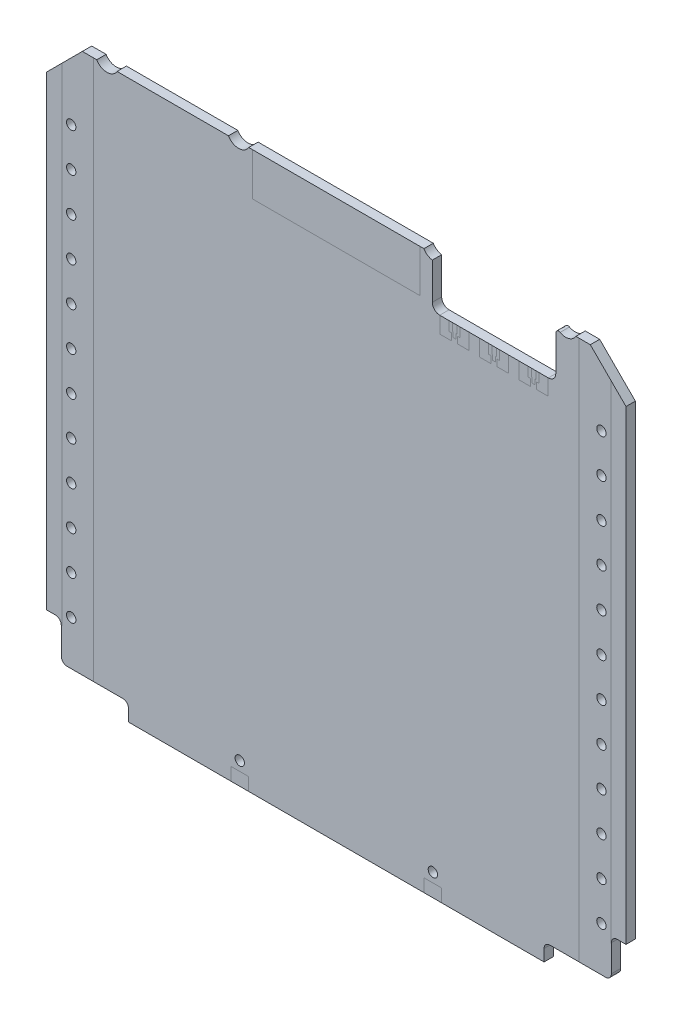
SolidWorks part; units mm, degrees
material "FR4_stuffedProtoboard"
ref_plane "Front Plane" through (0, 0, 0) normal (0, 0, 1) x (1, 0, 0)
ref_plane "Top Plane" through (0, 0, 0) normal (0, 1, 0) x (1, 0, 0)
ref_plane "Right Plane" through (0, 0, 0) normal (1, 0, 0) x (0, 0, -1)
ref_plane "Plane4" through (0, 0, -0.0125) normal (0, 0, -1) x (-1, 0, 0)
sketch "Sketch1" plane through (0, 0, -0.0125) normal (0, 0, -1) x (-1, 0, 0)
  line L4 (49.5, -50) -> (49.5, 45.3)
  line L6 (49.5, 45.3) -> (-49.5, 45.3)
  line L12 (-49.5, 45.3) -> (-49.5, -50)
  line L17 (-49.5, -50) -> (49.5, -50)
  line L18 (0, -50) -> (0, 45.3) construction
  dimension "D7" = 95.3
  dimension "D1" = 99
  dimension "D34" = 50
extrude "basicSize" add sketch "Sketch1" against normal blind 1.6
chamfer "Chamfer1" distance 6.1 angle 45 2 edges at (49.5, 45.3, 0.7875) (-49.5, 45.3, 0.7875)
sketch "Sketch4" plane through (0, 0, 1.5875) normal (0, 0, 1) x (1, 0, 0)
  line L1 (37.4679, 45.3) -> (40.9321, 45.3)
  line L7 (-43.4, 45.3) -> (43.4, 45.3) construction
  line L8 (49.5, 39.2) -> (49.5, -50) construction
  arc A0 (40.9321, 45.3) -> (37.4679, 45.3) centre (39.2, 46.3) cw
  point P5 (39.2, 44.3)
  dimension "D1" = 2
  dimension "D3" = 10.3
  dimension "D2" = 1
extrude "backplaneSideScrewCutout" cut sketch "Sketch4" against normal through all both and the other way through all
pattern_linear "LPattern3" count 2 spacing 22.5 along (-1, 0, 0) of "backplaneSideScrewCutout"
mirror "Mirror3" about plane through (0, 0, 0) normal (1, 0, 0) of "LPattern3"
sketch "Sketch6" plane through (0, 0, 1.5875) normal (0, 0, 1) x (1, 0, 0)
  line L0 (-49.5, -50) -> (-49.5, 39.2) construction
  line L1 (-49.5, -40.4) -> (-47, -40.4)
  line L2 (-49.5, -40.4) -> (-49.5, -50)
  line L4 (-47, -40.4) -> (-47, -47)
  line L5 (49.5, -50) -> (-49.5, -50) construction
  line L6 (-35.5, -50) -> (-49.5, -50)
  line L7 (-35.5, -50) -> (-35.5, -47)
  line L8 (-35.5, -47) -> (-47, -47)
  dimension "D1" = 2.5
  dimension "D2" = 3
  dimension "D3" = 9.6
  dimension "D4" = 14
extrude "Cut-Extrude4" cut sketch "Sketch6" against normal through all
fillet "Fillet1" radius 1 3 edges at (-35.5, -47, 0.7875) (-47, -47, 0.7875) (-47, -40.4, 0.7875)
mirror "Mirror1" about plane through (0, 0, 0) normal (1, 0, 0) of "Cut-Extrude4", "Fillet1"
sketch "Sketch7" plane through (0, 0, 1.5875) normal (0, 0, 1) x (1, 0, 0)
  line L0 (-14.2875, 45.5) -> (-14.2875, 39.912) construction
  line L1 (-14.2875, 45.3) -> (-14.2875, 38.007)
  line L2 (-12.2428, 38.007) -> (-11.8872, 38.007) construction
  line L3 (-14.2875, 38.007) -> (14.2875, 38.007)
  line L4 (14.2875, 45.5) -> (14.2875, 39.912) construction
  line L5 (14.2875, 45.3) -> (14.2875, 38.007)
  line L7 (-14.9679, 45.3) -> (14.9679, 45.3) construction
  line L8 (-14.2875, 45.3) -> (14.2875, 45.3)
extrude "TigerEyeFootprint" cut sketch "Sketch7" against normal blind 0.0001
sketch "thermalContacts_upper" plane through (0, 0, 1.5875) normal (0, 0, 1) x (1, 0, 0)
  line L0 (-49.5, -40.4) -> (-49.5, 39.2) construction
  line L1 (35.5, -50) -> (-35.5, -50) construction
  line L3 (-46.9, 45.3) -> (-46.9, -41.5)
  line L4 (-37.4679, 45.3) -> (-18.4321, 45.3) construction
  line L23 (-46.9, 45.3) -> (-56.3922, 45.3)
  line L24 (-56.3922, 45.3) -> (-56.3922, -41.5)
  line L25 (-56.3922, -41.5) -> (-46.9, -41.5)
  dimension "D1" = 2.6
  dimension "D2" = 8.5
extrude "keepOut_bottom" cut sketch "thermalContacts_upper" against normal blind 0.0001
sketch "Sketch3" plane through (0, 0, 1.5875) normal (0, 0, 1) x (1, 0, 0)
  line L1 (-47, -46) -> (-47, -41.5) construction
  line L2 (-36.5, -47) -> (-46, -47) construction
  line L3 (-14.9679, 45.3) -> (14.9679, 45.3) construction
  line L5 (-49.5, -40.4) -> (-49.5, 39.2) construction
  line L6 (-46.9, -41.5) -> (-46.9, 41.8) construction
  line L7 (-46.9, -41.5) -> (-47, -41.5)
  line L8 (-47, -46) -> (-47, -41.5) construction
  line L9 (-47, -41.5) -> (-46.9, -41.5) construction
  line L10 (0, -50) -> (0, 45.3) construction
  line L11 (35.5, -50) -> (-35.5, -50) construction
  line L12 (-43.4, 45.3) -> (-40.9321, 45.3) construction
  line L13 (-41.5, 45.3) -> (-46.9, 45.3)
  line L14 (-46, -47) -> (-41.5, -47)
  line L15 (-47, -41.5) -> (-47, -46)
  line L16 (-46.9, 45.3) -> (-46.9, -41.5)
  line L17 (-41.5, -47) -> (-41.5, 45.3)
  arc A3 (-47, -46) -> (-46, -47) centre (-46, -46) ccw construction
  arc A4 (-46, -47) -> (-47, -46) centre (-46, -46) cw
  dimension "D1" = 8
extrude "caution_top" cut sketch "Sketch3" against normal blind 0.0001
sketch "hold-downLocations" plane through (0, 0, 1.5875) normal (0, 0, 1) x (1, 0, 0)
  line L1 (-18, -47.8) -> (-15, -47.8) construction
  line L3 (15, -47.8) -> (18, -47.8)
  line L4 (18, -47.8) -> (18, -50)
  line L5 (35.5, -50) -> (-35.5, -50) construction
  line L6 (18, -50) -> (15, -50)
  line L7 (15, -50) -> (15, -47.8)
  line L8 (-15, -47.8) -> (-15, -50) construction
  line L9 (-15, -50) -> (-18, -50) construction
  line L10 (-18, -50) -> (-18, -47.8) construction
  line L11 (0, -50) -> (0, -47.8) construction
  line L12 (-15, -47.8) -> (15, -47.8) construction
  dimension "D1" = 3
  dimension "D2" = 2.2
  dimension "D3" = 3
  dimension "D5" = 30
extrude "hold-downFootprints" cut sketch "hold-downLocations" against normal blind 0.0001
ref_plane "midplane_Z" through (0, 0, 0.7875) normal (0, 0, 1) x (1, 0, 0)
mirror "clearances_top-bottom" about plane through (0, 0, 0.7875) normal (0, 0, 1) of "hold-downFootprints", "caution_top", "keepOut_bottom"
mirror "clearances_side-side" about plane through (0, 0, 0) normal (1, 0, 0) of "clearances_top-bottom"
sketch "Sketch10" plane through (0, 0, -0.0125) normal (0, 0, -1) x (-1, 0, 0)
  line L0 (-15, -47.8) -> (-15, -50) construction
  line L1 (-18, -47.8) -> (-15, -47.8)
  line L2 (-18, -47.8) -> (-18, -44.5)
  line L3 (-18, -44.5) -> (-15, -44.5)
  line L4 (-15, -47.8) -> (-15, -44.5)
  line L5 (-15, -50) -> (15, -50) construction
  line L6 (0, -50) -> (0, -41.5199) construction
  line L7 (15, -47.8) -> (15, -44.5)
  line L8 (18, -44.5) -> (15, -44.5)
  line L9 (18, -47.8) -> (18, -44.5)
  line L10 (18, -47.8) -> (15, -47.8)
  dimension "D1" = 5.5
extrude "bottomsideShelfKeepouts" cut sketch "Sketch10" against normal up to surface (0.0001 mm away) up to face at (16.5, -48.9, -0.0124)
sketch "recommendedBuildArea" [suppressed] plane through (0, 0, 1.5875) normal (0, 0, 1) x (1, 0, 0)
  line L0 (51.1146, 38.007) -> (51.1146, 56.8216) construction
  line L1 (-35.5, -45.5) -> (-46.8, -45.5) construction
  line L2 (-35.5, -47) -> (-35.5, -45.5) construction
  line L3 (35.5, -47) -> (35.5, -45.5) construction
  line L4 (14.2875, 45.3) -> (-14.2875, 45.3)
  line L5 (-14.2875, 45.3) -> (-14.2875, 38.007)
  line L6 (-14.2875, 38.007) -> (14.2875, 38.007)
  line L7 (-46.8, 41.9) -> (-49.5, 39.2)
  line L8 (-49.5, 39.2) -> (-49.5, -40.4)
  line L9 (-49.5, -40.4) -> (-48, -40.4)
  line L10 (-46.8, -41.5) -> (-46.8, 41.9)
  line L11 (-47, -41.4) -> (-47, -41.5)
  line L12 (-47, -41.4) -> (-47, -41.5)
  line L13 (-47, -41.5) -> (-46.8, -41.5)
  line L14 (35.5, -45.5) -> (46.8, -45.5) construction
  line L15 (54.1146, 35.007) -> (54.1146, 77.997)
  line L16 (54.1146, 77.997) -> (43.8, 42.325)
  line L17 (-46.8, -45.5) -> (-46.8, 41.9) construction
  line L20 (43.8, 42.325) -> (43.8, -42.5)
  line L21 (14.2875, 38.007) -> (14.2875, 45.3)
  line L22 (32.5, -42.5) -> (43.8, -42.5)
  line L23 (-14.2875, 45.3) -> (-14.2875, 38.007)
  line L24 (-14.2875, 38.007) -> (51.1146, 38.007)
  line L25 (32.5, -47) -> (32.5, -42.5)
  line L26 (32.5, -47) -> (32.5, -47)
  line L27 (21, -47) -> (32.5, -47)
  line L28 (21, -45) -> (21, -47)
  line L29 (46.8, -41.5) -> (47, -41.5)
  line L30 (46.8, -41.5) -> (47, -41.5)
  line L31 (46.8, 41.9) -> (46.8, -41.5)
  line L32 (48, -40.4) -> (49.5, -40.4)
  line L33 (49.5, -40.4) -> (49.5, 39.2)
  line L34 (49.5, 39.2) -> (46.8, 41.9)
  line L35 (47, -41.5) -> (47, -41.4)
  line L36 (12, -45) -> (21, -45)
  line L37 (47, -41.5) -> (47, -41.4)
  line L38 (46.8, 41.9) -> (46.8, -45.5) construction
  line L39 (12, -47) -> (12, -45)
  line L40 (-12, -47) -> (12, -47)
  line L41 (-12, -45) -> (-12, -47)
  line L42 (-21, -45) -> (-12, -45)
  line L43 (-21, -47) -> (-21, -45)
  line L44 (-32.5, -47) -> (-21, -47)
  line L45 (-32.5, -47) -> (-32.5, -47)
  line L46 (-32.5, -47) -> (-32.5, -42.5)
  line L47 (-32.5, -42.5) -> (-43.8, -42.5)
  line L48 (-43.8, -42.5) -> (-43.8, 34.7661)
  line L49 (-43.8, 34.7661) -> (-43.8, 34.7661)
  line L50 (-43.8, 34.7661) -> (-39.8793, 42.3)
  line L51 (-17.2875, 42.3) -> (-39.8793, 42.3)
  line L52 (-17.2875, 42.3) -> (-17.2875, 35.007)
  line L53 (-17.2875, 35.007) -> (54.1146, 35.007)
  line L59 (-47, -41.5) -> (-46.8, -41.5)
  line L72 (-15, -48) -> (-15, -50)
  line L73 (-15, -50) -> (15, -50)
  line L74 (15, -50) -> (15, -48)
  line L75 (15, -48) -> (18, -48)
  line L76 (18, -48) -> (18, -50)
  line L77 (18, -50) -> (35.5, -50)
  line L78 (35.5, -50) -> (35.5, -48)
  line L79 (36.5, -47) -> (41.5, -47)
  line L80 (41.5, -47) -> (41.5, 45.3)
  line L81 (41.5, 45.3) -> (40.9321, 45.3)
  line L82 (37.4679, 45.3) -> (34.25, 45.3)
  line L83 (34.25, 45.3) -> (34.25, 38.35)
  line L84 (34.25, 38.35) -> (30.75, 38.35)
  line L85 (30.75, 38.35) -> (30.75, 45.3)
  line L86 (30.75, 45.3) -> (29.25, 45.3)
  line L87 (29.25, 45.3) -> (29.25, 38.35)
  line L88 (29.25, 38.35) -> (25.75, 38.35)
  line L89 (25.75, 38.35) -> (25.75, 45.3)
  line L90 (25.75, 45.3) -> (24.25, 45.3)
  line L91 (24.25, 45.3) -> (24.25, 38.35)
  line L92 (24.25, 38.35) -> (20.75, 38.35)
  line L93 (20.75, 38.35) -> (20.75, 45.3)
  line L94 (20.75, 45.3) -> (18.4321, 45.3)
  line L95 (14.9679, 45.3) -> (14.2875, 45.3)
  line L96 (14.2875, 45.3) -> (14.2875, 38.007)
  line L97 (14.2875, 38.007) -> (-14.2875, 38.007)
  line L98 (-14.2875, 38.007) -> (-14.2875, 45.3)
  line L99 (-14.2875, 45.3) -> (-14.9679, 45.3)
  line L100 (-18.4321, 45.3) -> (-37.4679, 45.3)
  line L101 (-40.9321, 45.3) -> (-41.5, 45.3)
  line L102 (41.5, -47) -> (41.5, 45.3)
  line L103 (-41.5, -47) -> (-36.5, -47)
  line L104 (-35.5, -48) -> (-35.5, -50)
  line L105 (-35.5, -50) -> (-18, -50)
  line L106 (-18, -50) -> (-18, -48)
  line L107 (-18, -48) -> (-15, -48)
  line L108 (-15, -48) -> (-15, -50) construction
  line L109 (-15, -50) -> (15, -50) construction
  line L110 (15, -50) -> (15, -48) construction
  line L111 (15, -48) -> (18, -48) construction
  line L112 (18, -48) -> (18, -50) construction
  line L113 (18, -50) -> (35.5, -50) construction
  line L114 (35.5, -50) -> (35.5, -47) construction
  line L115 (35.5, -47) -> (41.5, -47) construction
  line L133 (51.1146, 38.007) -> (-14.2875, 38.007)
  line L134 (-14.2875, 38.007) -> (-14.2875, 45.3)
  line L136 (-14.2875, 45.3) -> (-41.7, 45.3) construction
  line L139 (-41.5, -47) -> (-35.5, -47) construction
  line L140 (-35.5, -47) -> (-35.5, -50) construction
  line L141 (-35.5, -50) -> (-18, -50) construction
  line L142 (-18, -50) -> (-18, -48) construction
  line L143 (-18, -48) -> (-15, -48) construction
  line L144 (-46.8, 35.5) -> (-41.7, 45.3) construction
  line L160 (-41.5, 45.3) -> (-41.5, -47)
  line L161 (-41.5, 45.3) -> (-41.5, -47)
  line L162 (-46.8, 41.9) -> (-46.8, 35.5) construction
  line L163 (51.1146, 56.8216) -> (46.8, 41.9) construction
  arc A1 (-47, -41.4) -> (-48, -40.4) centre (-48, -41.4) ccw
  arc A3 (48, -40.4) -> (47, -41.4) centre (48, -41.4) ccw
  arc A10 (36.5, -47) -> (35.5, -48) centre (36.5, -48) ccw
  arc A11 (37.4679, 45.3) -> (40.9321, 45.3) centre (39.2, 46.3) ccw
  arc A12 (14.9679, 45.3) -> (18.4321, 45.3) centre (16.7, 46.3) ccw
  arc A13 (-18.4321, 45.3) -> (-14.9679, 45.3) centre (-16.7, 46.3) ccw
  arc A14 (-40.9321, 45.3) -> (-37.4679, 45.3) centre (-39.2, 46.3) ccw
  arc A15 (-35.5, -48) -> (-36.5, -47) centre (-36.5, -48) ccw
  dimension "D5" = 1.5
  dimension "D1" = 0
  dimension "D2" = 0
  dimension "D3" = 0
  dimension "D4" = 0
  dimension "D6" = 3
ref_point "rail midpoint"
sketch "locatorSketch" plane through (0, 0, 1.5875) normal (0, 0, 1) x (1, 0, 0)
  line L0 (-12.2428, 39.531) -> (12.2428, 38.007) construction
  line L1 (12.2428, 39.531) -> (-12.2428, 38.007) construction
  line L2 (-21.9628, 39.277) -> (-33.0372, 38.261) construction
  line L3 (-33.0372, 39.277) -> (-21.9628, 38.261) construction
  line L4 (-12.2428, 38.261) -> (-12.2428, 38.007)
  line L5 (-11.8872, 38.261) -> (-12.2428, 38.261)
  line L6 (-11.8872, 38.007) -> (-11.8872, 38.261)
  line L7 (-12.2428, 38.007) -> (-11.8872, 38.007)
  line L8 (-12.2428, 38.261) -> (-12.2428, 38.007)
  line L9 (-11.8872, 38.261) -> (-12.2428, 38.261)
  line L10 (-11.8872, 38.007) -> (-11.8872, 38.261)
  line L11 (-12.2428, 38.007) -> (-11.8872, 38.007)
  line L12 (-12.2428, 39.531) -> (-12.2428, 39.277)
  line L13 (-11.8872, 39.531) -> (-12.2428, 39.531)
  line L14 (-11.8872, 39.277) -> (-11.8872, 39.531)
  line L15 (-12.2428, 39.277) -> (-11.8872, 39.277)
  line L16 (-12.2428, 39.531) -> (-12.2428, 39.277)
  line L17 (-11.8872, 39.531) -> (-12.2428, 39.531)
  line L18 (-11.8872, 39.277) -> (-11.8872, 39.531)
  line L19 (-12.2428, 39.277) -> (-11.8872, 39.277)
  line L20 (11.8872, 39.531) -> (11.8872, 39.277)
  line L21 (12.2428, 39.531) -> (11.8872, 39.531)
  line L22 (12.2428, 39.277) -> (12.2428, 39.531)
  line L23 (11.8872, 39.277) -> (12.2428, 39.277)
  line L24 (11.8872, 39.531) -> (11.8872, 39.277)
  line L25 (12.2428, 39.531) -> (11.8872, 39.531)
  line L26 (12.2428, 39.277) -> (12.2428, 39.531)
  line L27 (11.8872, 39.277) -> (12.2428, 39.277)
  line L28 (11.8872, 38.261) -> (11.8872, 38.007)
  line L29 (12.2428, 38.261) -> (11.8872, 38.261)
  line L30 (12.2428, 38.007) -> (12.2428, 38.261)
  line L31 (11.8872, 38.007) -> (12.2428, 38.007)
  line L32 (11.8872, 38.261) -> (11.8872, 38.007)
  line L33 (12.2428, 38.261) -> (11.8872, 38.261)
  line L34 (12.2428, 38.007) -> (12.2428, 38.261)
  line L35 (11.8872, 38.007) -> (12.2428, 38.007)
  line L38 (-21.9628, 39.531) -> (-21.9628, 39.277)
  line L39 (-21.6072, 39.531) -> (-21.9628, 39.531)
  line L40 (-21.6072, 39.277) -> (-21.6072, 39.531)
  line L41 (-21.9628, 39.277) -> (-21.6072, 39.277)
  line L42 (-21.9628, 39.531) -> (-21.9628, 39.277)
  line L43 (-21.6072, 39.531) -> (-21.9628, 39.531)
  line L44 (-21.6072, 39.277) -> (-21.6072, 39.531)
  line L45 (-21.9628, 39.277) -> (-21.6072, 39.277)
  line L46 (-33.3928, 38.261) -> (-33.3928, 38.007)
  line L47 (-33.0372, 38.261) -> (-33.3928, 38.261)
  line L48 (-33.0372, 38.007) -> (-33.0372, 38.261)
  line L49 (-33.3928, 38.007) -> (-33.0372, 38.007)
  line L50 (-33.3928, 38.261) -> (-33.3928, 38.007)
  line L51 (-33.0372, 38.261) -> (-33.3928, 38.261)
  line L52 (-33.0372, 38.007) -> (-33.0372, 38.261)
  line L53 (-33.3928, 38.007) -> (-33.0372, 38.007)
  line L55 (-21.9628, 38.261) -> (-21.9628, 38.007)
  line L56 (-21.6072, 38.261) -> (-21.9628, 38.261)
  line L57 (-21.6072, 38.007) -> (-21.6072, 38.261)
  line L58 (-21.9628, 38.007) -> (-21.6072, 38.007)
  line L59 (-21.9628, 38.261) -> (-21.9628, 38.007)
  line L60 (-21.6072, 38.261) -> (-21.9628, 38.261)
  line L61 (-21.6072, 38.007) -> (-21.6072, 38.261)
  line L62 (-21.9628, 38.007) -> (-21.6072, 38.007)
  line L63 (-33.3928, 39.531) -> (-33.3928, 39.277)
  line L64 (-33.0372, 39.531) -> (-33.3928, 39.531)
  line L65 (-33.0372, 39.277) -> (-33.0372, 39.531)
  line L66 (-33.3928, 39.277) -> (-33.0372, 39.277)
  line L67 (-33.3928, 39.531) -> (-33.3928, 39.277)
  line L68 (-33.0372, 39.531) -> (-33.3928, 39.531)
  line L69 (-33.0372, 39.277) -> (-33.0372, 39.531)
  line L70 (-33.3928, 39.277) -> (-33.0372, 39.277)
  dimension "D1" = 0
  dimension "D2" = 0
  dimension "D3" = 0
  dimension "D4" = 0
  dimension "D5" = 0
  dimension "D6" = 0
  dimension "D7" = 0
  dimension "D8" = 0
sketch "Sketch8" plane through (0, 0, 1.5875) normal (0, 0, 1) x (1, 0, 0)
  line L0 (-49.5, -40.4) -> (-48, -40.4) construction
  line L2 (-49.5, -40.4) -> (-49.5, 39.2) construction
  line L3 (-41.5, 45.3) -> (-43.4, 45.3) construction
  line L4 (-18, -47.8) -> (-15, -47.8) construction
  line L5 (-45.3, 33.5) -> (-46.9, 33.5) construction
  line L6 (-46.9, 41.8) -> (-46.9, -41.5) construction
  line L7 (-16.5, -46.2) -> (-16.5, -47.8) construction
  line L8 (-18, -47.8) -> (-15, -47.8) construction
  circle A0 centre (-45.3, 33.5) radius 0.8
  circle A1 centre (-45.3, 26.8727) radius 0.8
  circle A2 centre (-45.3, 20.2455) radius 0.8
  circle A3 centre (-45.3, 13.6182) radius 0.8
  circle A4 centre (-45.3, 6.9909) radius 0.8
  circle A5 centre (-45.3, 0.3636) radius 0.8
  circle A6 centre (-45.3, -6.2636) radius 0.8
  circle A7 centre (-45.3, -12.8909) radius 0.8
  circle A8 centre (-45.3, -19.5182) radius 0.8
  circle A9 centre (-45.3, -26.1455) radius 0.8
  circle A10 centre (-45.3, -32.7727) radius 0.8
  circle A11 centre (-45.3, -39.4) radius 0.8
  circle A12 centre (-16.5, -46.2) radius 0.8
  point P35 (-16.5, -47.8)
  dimension "D1" = 1.6
  dimension "D3" = 1
  dimension "D5" = 4.2
  dimension "D6" = 11.8
  dimension "D2" = 12
extrude "springPinHoleSeed" cut sketch "Sketch8" against normal blind 10
mirror "Mirror4" about plane through (0, 0, 0) normal (1, 0, 0) of "springPinHoleSeed"
sketch "Sketch9" plane through (0, 0, 1.5875) normal (0, 0, 1) x (1, 0, 0)
  circle A0 centre (-45.3, 33.5) radius 1.35
  dimension "D1" = 2.7
sketch "bottomsideKeepout_trace" plane through (0, 0, -0.0125) normal (0, 0, -1) x (-1, 0, 0)
  line L0 (18, -50) -> (18, -44.5) construction
  line L1 (18, -44.5) -> (15, -44.5) construction
  line L2 (15, -44.5) -> (15, -50) construction
  line L3 (-15, -44.5) -> (-15, -50) construction
  line L4 (-15, -44.5) -> (-18, -44.5) construction
  line L5 (-18, -50) -> (-18, -44.5) construction
  line L6 (18, -50) -> (18, -44.5)
  line L7 (18, -44.5) -> (15, -44.5)
  line L8 (15, -44.5) -> (15, -50)
  line L9 (-15, -44.5) -> (-15, -50)
  line L10 (-15, -44.5) -> (-18, -44.5)
  line L11 (-18, -50) -> (-18, -44.5)
  line L12 (15, -50) -> (18, -50) construction
  line L13 (-15, -50) -> (-18, -50) construction
  line L14 (15, -50) -> (18, -50)
  line L15 (-15, -50) -> (-18, -50)
sketch "Sketch11" plane through (0, 0, 1.5875) normal (0, 0, 1) x (1, 0, 0)
  line L0 (18.4321, 45.3) -> (37.4679, 45.3) construction
  line L1 (16.4, 45.3) -> (37.5, 45.3)
  line L2 (16.4, 45.3) -> (16.4, 36.8)
  line L3 (16.4, 36.8) -> (24.95, 36.8)
  line L4 (37.5, 45.3) -> (37.5, 36.8)
  line L5 (16.4, 45.3) -> (37.5, 36.8) construction
  line L6 (16.4, 36.8) -> (37.5, 45.3) construction
  line L7 (49.5, 39.2) -> (49.5, -40.4) construction
  line L8 (26.95, 36.8) -> (26.95, 45.3) construction
  line L9 (24.95, 36.8) -> (28.95, 36.8)
  line L10 (28.95, 36.8) -> (37.5, 36.8)
  point P4 (26.95, 41.05)
  point P9 (0, 0)
  point P10 (0, 0)
  point P12 (28.8548, 36.8)
  point P21 (0, 0)
  dimension "D1" = 21.1
  dimension "D2" = 12
  dimension "D3" = 8.5
  dimension "D4" = 4
extrude "Cut-Extrude5" cut sketch "Sketch11" against normal blind 10
fillet "Fillet3" radius 1.27 2 edges at (37.5, 36.8, 0.7875) (16.4, 36.8, 0.7875)
sketch "Sketch12" plane through (0, 0, 1.5875) normal (0, 0, 1) x (1, 0, 0)
  line L0 (17.67, 36.8) -> (36.23, 36.8) construction
  line L1 (19.25, 36.8) -> (17.75, 36.8)
  line L2 (19.25, 36.8) -> (19.25, 35.2)
  line L3 (19.25, 35.2) -> (17.75, 35.2)
  line L4 (17.75, 36.8) -> (17.75, 35.2)
  line L5 (19.25, 36.8) -> (17.75, 35.2) construction
  line L6 (19.25, 35.2) -> (17.75, 36.8) construction
  line L7 (20.2, 36.8) -> (20.2, 34.2278) construction
  line L8 (20.585, 36.8) -> (19.815, 36.8)
  line L9 (20.585, 36.8) -> (20.585, 35.5)
  line L10 (20.585, 35.5) -> (19.815, 35.5)
  line L11 (19.815, 36.8) -> (19.815, 35.5)
  line L12 (20.585, 36.8) -> (19.815, 35.5) construction
  line L13 (20.585, 35.5) -> (19.815, 36.8) construction
  line L14 (21.15, 36.8) -> (22.65, 36.8)
  line L15 (21.15, 36.8) -> (21.15, 35.2)
  line L16 (21.15, 35.2) -> (22.65, 35.2)
  line L17 (22.65, 36.8) -> (22.65, 35.2)
  line L18 (21.15, 36.8) -> (22.65, 35.2) construction
  line L19 (21.15, 35.2) -> (22.65, 36.8) construction
  line L21 (22.65, 35.2) -> (20.725, 35.2)
  line L22 (22.65, 35.2) -> (22.65, 34.069)
  line L23 (22.65, 34.069) -> (20.725, 34.069)
  line L24 (20.725, 35.2) -> (20.725, 34.069)
  line L25 (22.65, 35.2) -> (20.725, 34.069) construction
  line L26 (22.65, 34.069) -> (20.725, 35.2) construction
  line L27 (20.43, 35.5) -> (19.97, 35.5)
  line L28 (20.43, 35.5) -> (20.43, 34.6345)
  line L29 (20.43, 34.6345) -> (19.97, 34.6345)
  line L30 (19.97, 35.5) -> (19.97, 34.6345)
  line L31 (20.43, 35.5) -> (19.97, 34.6345) construction
  line L32 (20.43, 34.6345) -> (19.97, 35.5) construction
  line L33 (17.75, 35.2) -> (19.675, 35.2)
  line L34 (17.75, 35.2) -> (17.75, 34.0035)
  line L35 (17.75, 34.0035) -> (19.675, 34.0035)
  line L36 (19.675, 35.2) -> (19.675, 34.0035)
  line L37 (17.75, 35.2) -> (19.675, 34.0035) construction
  line L38 (17.75, 34.0035) -> (19.675, 35.2) construction
  line L39 (16.4, 44.3226) -> (16.4, 38.07) construction
  point P4 (18.5, 36)
  point P11 (20.2, 36.15)
  point P16 (21.9, 36)
  point P17 (17.6689, 35.2)
  point P23 (21.6875, 34.6345)
  point P28 (20.2, 35.0673)
  point P33 (18.7125, 34.6017)
  point P34 (22.6329, 35.213)
  line M28 (36.23, 36.8) -> (17.67, 36.8)
  dimension "D1" = 0.77
  dimension "D2" = 1.9
  dimension "D3" = 1.3
  dimension "D4" = 1.6
  dimension "D5" = 4.9
  dimension "D6" = 0.46
  dimension "D7" = 1.05
  dimension "D8" = 3.8
extrude "Boss-Extrude1" add sketch "Sketch12" along normal blind 0.001 contours L17 L15 L16 M28 | L21 L24 L23 L22 L16 | L11 L10 L9 M28 | L10 L30 L29 L28 | L36 L33 L3 L34 L35 | L4 L3 L2 M28 region at (18.5, 36, 1.5875) region at (21.9, 36, 1.5875) region at (20.2, 36.15, 1.5875) region at (18.7125, 34.6017, 1.5875) region at (20.2, 35.0673, 1.5875) region at (21.6875, 34.6345, 1.5875)
pattern_linear "LPattern4" count 3 spacing 6.75 along (1, 0, 0) of "Boss-Extrude1"
fillet "Fillet4" radius 0.5 1 edges at (37.5, 45.2464, 0.7875)
